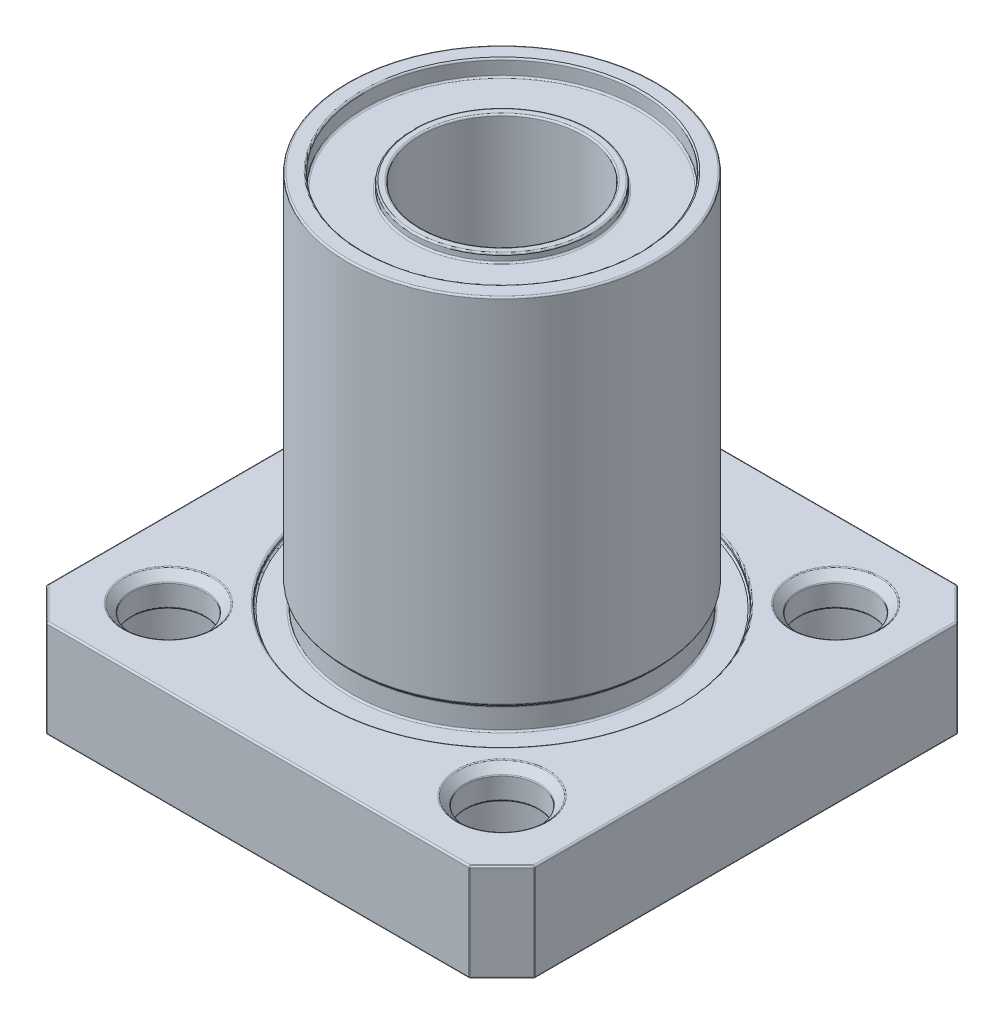
SolidWorks part; units mm, degrees
ref_plane "Front Plane" through (0, 0, 0) normal (0, 0, 1) x (1, 0, 0)
ref_plane "Top Plane" through (0, 0, 0) normal (0, 1, 0) x (1, 0, 0)
ref_plane "Right Plane" through (0, 0, 0) normal (1, 0, 0) x (0, 0, -1)
sketch "Sketch1" plane through (0, 0, 0) normal (0, 1, 0) x (1, 0, 0)
  line L1 (-15, -15) -> (15, -15)
  line L2 (-15, -15) -> (-15, 15)
  line L3 (-15, 15) -> (15, 15)
  line L4 (15, -15) -> (15, 15)
  line L5 (-15, -15) -> (15, 15) construction
  line L6 (-15, 15) -> (15, -15) construction
  point P0 (0, 0)
  dimension "D1" = 30
extrude "Boss-Extrude1" add sketch "Sketch1" along normal blind 6
sketch "Sketch2" plane through (0, 6, 0) normal (0, 1, 0) x (1, 0, 0)
  circle A0 centre (0, 0) radius 9.5
  dimension "D1" = 19
extrude "Boss-Extrude2" add sketch "Sketch2" along normal blind 23
sketch "Sketch3" plane through (0, 6, 0) normal (0, 1, 0) x (1, 0, 0)
  line L0 (-15, 15) -> (15, -15) construction
  line L1 (-15, -15) -> (15, 15) construction
  circle A0 centre (-10.253, 10.253) radius 2.25
  circle A1 centre (10.253, 10.253) radius 2.25
  circle A2 centre (10.253, -10.253) radius 2.25
  circle A3 centre (-10.253, -10.253) radius 2.25
  dimension "D1" = 4.5
extrude "Cut-Extrude3" cut sketch "Sketch3" against normal up to next
chamfer "Chamfer2" distance 2 angle 45 4 edges at (15, 3, -15) (15, 3, 15) (-15, 3, 15) (-15, 3, -15)
sketch "Sketch6" plane through (0, 29, 0) normal (0, 1, 0) x (1, 0, 0)
  circle A0 centre (0, 0) radius 8.5
  circle A1 centre (0, 0) radius 9.5 construction
  dimension "D1" = 1
extrude "Cut-Extrude4" cut sketch "Sketch6" against normal through all
sketch "Sketch7" plane through (0, 6, 0) normal (0, 1, 0) x (1, 0, 0)
  line L0 (-15, 15) -> (15, -15) construction
  circle A0 centre (0, 0) radius 10.8
  circle M5 centre (0, 0) radius 9.5
  dimension "D1" = 21.6
extrude "Cut-Extrude6" cut sketch "Sketch7" against normal blind 0.3 contours A0 M5 region at (-10.4945, 6, 0)
ref_axis "Axis2" through (0, 29, 0) along (0, -1, 0)
sketch "Sketch8" plane through (0, 0, 0) normal (0, 0, 1) x (1, 0, 0)
  line L0 (-9.5, 7.3) -> (-9.5, 5.7)
  line L1 (-9.5, 29) -> (-9.5, 5.7) construction
  line L2 (-9.5, 5.7) -> (-9.25, 5.7)
  line L3 (-9.25, 5.7) -> (-9.25, 7.05)
  line L4 (-9.25, 7.05) -> (-9.5, 7.3)
  line L5 (9.5, 6) -> (-9.5, 6) construction
  dimension "D1" = 1.6
  dimension "D2" = 0.25
  dimension "D3" = 0.25
  dimension "D4" = 0.3
revolve "Cut-Revolve1" cut sketch "Sketch8" angle 360 about axis through (0, 29, 0) along (0, -1, 0)
ref_plane "Plane1" through (0, 28, 0) normal (0, 1, 0) x (1, 0, 0)
sketch "Sketch9" plane through (0, 28, 0) normal (0, 1, 0) x (1, 0, 0)
  line L0 (-15, 15) -> (15, -15) construction
  circle A0 centre (0, 0) radius 8.5
  circle A1 centre (0, 0) radius 5
  dimension "D1" = 10
extrude "Boss-Extrude3" add sketch "Sketch9" against normal blind 27
sketch "Sketch10" plane through (0, 28, 0) normal (0, 1, 0) x (1, 0, 0)
  line L0 (-15, 15) -> (15, -15) construction
  circle A0 centre (0, 0) radius 5
  circle A1 centre (0, 0) radius 5.5
  dimension "D1" = 0.5
extrude "Boss-Extrude4" add sketch "Sketch10" along normal blind 0.5
chamfer "Chamfer3" distance 0.5 angle 45 4 edges at (10.253, 6, 12.503) (10.253, 6, -8.003) (-10.253, 6, 12.503) (-10.253, 6, -8.003)
sketch "Sketch12" plane through (0, 0, 0) normal (0, -1, 0) x (1, 0, 0)
  line L0 (-15, -15) -> (15, 15) construction
  line L1 (-15, 15) -> (15, -15) construction
  circle A0 centre (-10.253, 10.253) radius 3.75
  circle A1 centre (10.253, 10.253) radius 3.75
  circle A2 centre (-10.253, -10.253) radius 3.75
  circle A3 centre (10.253, -10.253) radius 3.75
  dimension "D1" = 7.5
extrude "Cut-Extrude7" cut sketch "Sketch12" against normal blind 4.1
fillet "Fillet2" radius 0.1 49 edges at (0, 1, 8.5) (-15, 0, 0) (14, 0, 14) (15, 3, 13) (15, 0, 0) (14, 0, -14) (15, 3, -13) (0, 0, -15) (13, 3, -15) (-15, 3, -13) (-14, 0, -14) (-13, 3, -15) (-14, 0, 14) (-15, 3, 13) (-13, 3, 15) (13, 3, 15) (0, 0, 15) (-10.253, 4.1, -12.503) (-10.253, 5.5, -12.503) (10.253, 4.1, 8.003) (10.253, 5.5, 8.003) (-10.253, 4.1, 8.003) (-10.253, 5.5, 8.003) (10.253, 4.1, -12.503) (10.253, 5.5, -12.503) (14, 6, 14) (0, 6, 15) (-14, 6, 14) (-15, 6, 0) (-14, 6, -14) (0, 6, -15) (14, 6, -14) (15, 6, 0) (0, 6, 10.8) (-10.253, 6, -13.003) (-10.253, 6, 7.503) (10.253, 6, -13.003) (10.253, 6, 7.503) (0, 5.7, 10.8) (0, 7.3, 9.5) (0, 5.7, 9.25) (0, 7.05, 9.25) (0, 29, 9.5) (0, 29, 8.5) (0, 28, 5.5) (0, 28, 8.5) (0, 28.5, 5.5) (0, 28.5, 5) (0, 0, 8.5)
chamfer "Chamfer4" distance 0.5 angle 45 4 edges at (-10.253, 0, -14.003) (10.253, 0, -14.003) (10.253, 0, 6.503) (-10.253, 0, 6.503)
